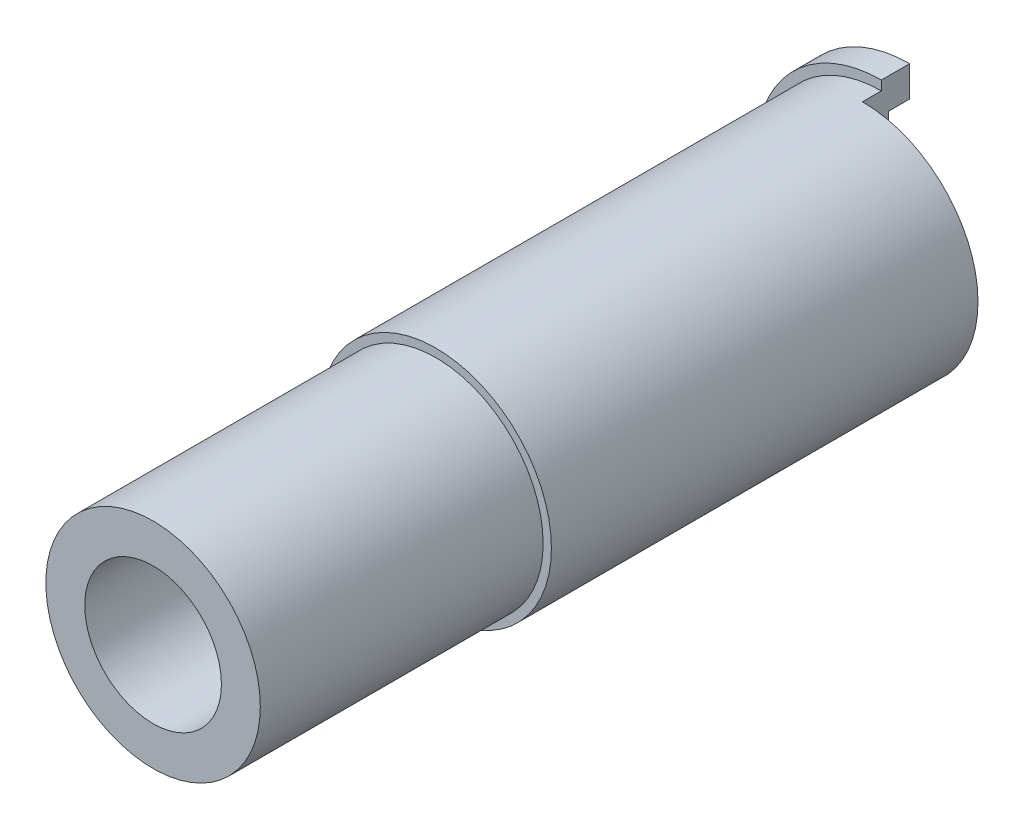
SolidWorks part; units mm, degrees
ref_plane "Plan de face" through (0, 0, 0) normal (0, 0, 1) x (1, 0, 0)
ref_plane "Plan de dessus" through (0, 0, 0) normal (0, 1, 0) x (1, 0, 0)
ref_plane "Plan de droite" through (0, 0, 0) normal (1, 0, 0) x (0, 0, -1)
sketch "Esquisse1" plane through (0, 0, 0) normal (0, 0, 1) x (1, 0, 0)
  circle A0 centre (0, 0) radius 2.9
  circle A1 centre (0, 0) radius 4.55
  circle A2 centre (0, 0) radius 4.9
  dimension "D1" = 5.8
  dimension "D2" = 9.1
  dimension "D3" = 9.8
extrude "Boss.-Extru.1" add sketch "Esquisse1" along normal blind 12 contours A1 A0 region at (-4.4213, 0, 0)
extrude "Boss.-Extru.2" add sketch "Esquisse1<3>" against normal blind 19.2 contours A1 A0 | A2 A1 region at (-4.4213, 0, 0) region at (-4.7614, 0, 0)
sketch "Esquisse1<3>" plane through (0, 0, 0) normal (0, 0, 1) x (1, 0, 0) same geometry as "Esquisse1"
sketch "Esquisse2" plane through (0, 0, 0) normal (0, 1, 0) x (1, 0, 0)
  line L0 (4.9, 19.2) -> (-4.9, 19.2) construction
  line L1 (6.7681, 19.2) -> (0, 19.2)
  line L2 (0, 19.2) -> (0, 18.1)
  line L3 (0, 18.1) -> (6.7681, 18.1)
  line L4 (6.7681, 18.1) -> (6.7681, 19.2)
  dimension "D1" = 1.1
extrude "Enlèv. mat.-Extru.1" cut sketch "Esquisse2" against normal mid plane 10
sketch "Esquisse3" plane through (0, 0, 0) normal (1, 0, 0) x (0, 0, -1)
  line L0 (18.1, -4.9) -> (19.2, -4.9) construction
  line L1 (18.9, -4.9) -> (19.2, -4.9)
  line L2 (18.9, -4.9) -> (18.9, -5.3)
  line L3 (18.9, -5.3) -> (20.1, -5.3)
  line L4 (20.1, -5.3) -> (20.1, -4)
  line L5 (20.1, -4) -> (19.2, -4)
  line L6 (19.2, -4) -> (19.2, -4.9)
  line L7 (0, 0) -> (23.1095, 0) construction
  dimension "D1" = 1.2
  dimension "D2" = 0.3
  dimension "D3" = 5.3
  dimension "D4" = 4
revolve "Révolution1" add sketch "Esquisse3" angle 180 about L7
